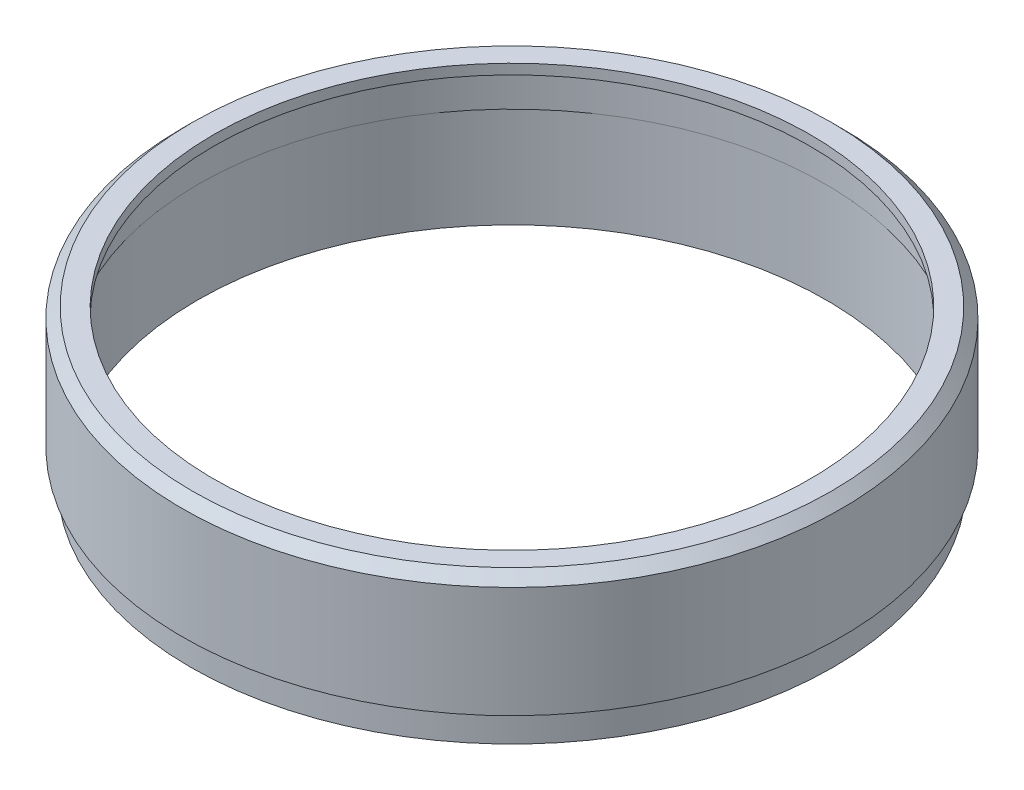
SolidWorks part; units mm, degrees
ref_plane "Front Plane" through (0, 0, 0) normal (0, 0, 1) x (1, 0, 0)
ref_plane "Top Plane" through (0, 0, 0) normal (0, 1, 0) x (1, 0, 0)
ref_plane "Right Plane" through (0, 0, 0) normal (1, 0, 0) x (0, 0, -1)
ref_axis "Axis1" through (0, 0, 0) along (0, 1, 0)
sketch "Sketch1" plane through (0, 0, 0) normal (0, 0, 1) x (1, 0, 0)
  line L0 (0, 0) -> (0, -50000) construction
  line L1 (-32.65, 4) -> (-31.85, 4)
  line L2 (31.9, 4) -> (-31.9, 4) construction
  line L3 (-31.85, 4) -> (-31.85, 1)
  line L4 (31.9, 1) -> (-31.9, 1) construction
  line L5 (-31.85, 1) -> (-31.15, 1)
  line L6 (-31.15, 1) -> (-31.15, 11)
  line L7 (-31.9, 4) -> (-31.9, 1) construction
  line L8 (-32.65, 4) -> (-32.65, 15)
  line L9 (-31.15, 11) -> (-31.05, 11)
  line L10 (-31.05, 11) -> (-31.05, 15)
  line L11 (-31.05, 15) -> (-29.55, 15)
  line L12 (-31, 11) -> (31, 11) construction
  line L15 (-29.55, 15) -> (-29.55, 16)
  line L24 (-29.55, 16) -> (-31.65, 16)
  line L25 (-31.65, 16) -> (-32.65, 15)
  dimension "D1" = 0.05
  dimension "D2" = 62.1
  dimension "D3" = 1.5
  dimension "D4" = 4
  dimension "D5" = 1.5
  dimension "D6" = 1
  dimension "D7" = 1
  dimension "D10" = 135
revolve "Revolve1" add sketch "Sketch1" angle 360 about L0
